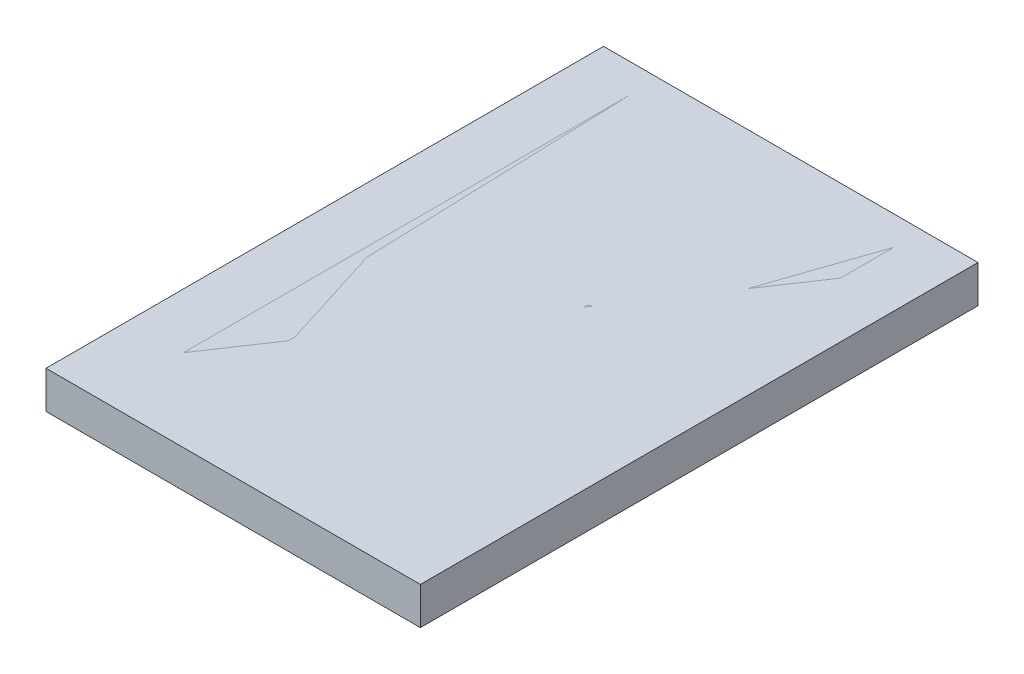
SolidWorks part; units mm, degrees
other "Part"
other "Stock"
ref_plane "Front Plane" through (0, 0, 0) normal (0, 0, 1) x (1, 0, 0)
ref_plane "Top Plane" through (0, 0, 0) normal (0, 1, 0) x (1, 0, 0)
ref_plane "Right Plane" through (0, 0, 0) normal (1, 0, 0) x (0, 0, -1)
sketch "Sketch1" plane through (0, 0, 0) normal (0, 1, 0) x (1, 0, 0)
  line L0 (28.2, 0) -> (28.2, -112.8) construction
  line L1 (0, 0) -> (56.4, 0)
  line L2 (0, 0) -> (0, -112.8)
  line L3 (0, -112.8) -> (56.4, -112.8)
  line L4 (56.4, 0) -> (56.4, -112.8)
  line L5 (0, -56.4) -> (56.4, -56.4) construction
  dimension "D1" = 56.4
  dimension "D2" = 112.8
extrude "Boss-Extrude1" add sketch "Sketch1" along normal blind 8
sketch "Sketch2" plane through (0, 8, 0) normal (0, 1, 0) x (1, 0, 0)
  line L0 (0, -56.4) -> (56.4, -56.4) construction
  line L1 (0, 0) -> (0, -112.8) construction
  line L2 (56.4, -112.8) -> (56.4, 0) construction
  line L3 (28.2, 0) -> (28.2, -112.8) construction
  line L4 (56.4, 0) -> (0, 0) construction
  line L5 (0, -112.8) -> (56.4, -112.8) construction
  line L6 (0, -28.2) -> (56.4, -28.2) construction
  circle A0 centre (28.2, -28.2) radius 19.25
  dimension "D2" = 38.5
  dimension "D1" = 28.2
extrude "Cut-Extrude1" cut sketch "Sketch2" against normal blind 2
sketch "Sketch3" plane through (0, 6, 0) normal (0, 1, 0) x (1, 0, 0)
  circle A0 centre (28.2, -28.2) radius 5
  dimension "D1" = 10
extrude "Cut-Extrude2" cut sketch "Sketch3" against normal through all
sketch "Sketch4" plane through (0, 8, 0) normal (0, 1, 0) x (1, 0, 0)
  line L0 (56.4, 0) -> (0, 0) construction
  line L1 (28.2, 0) -> (28.2, -86.1901) construction
  line L2 (0, -28.2) -> (56.4, -28.2) construction
  line L3 (0, 0) -> (0, -112.8) construction
  line L4 (56.4, -112.8) -> (56.4, 0) construction
  line L5 (0, -56.4) -> (56.4, -56.4) construction
  circle A0 centre (4.58, -4.58) radius 2.65
  circle A1 centre (51.82, -4.58) radius 2.65
  circle A2 centre (51.82, -51.82) radius 2.65
  circle A3 centre (4.58, -51.82) radius 2.65
  dimension "D4" = 5.3
  dimension "D1" = 23.62
  dimension "D2" = 28.2
  dimension "D3" = 23.62
extrude "Cut-Extrude3" cut sketch "Sketch4" against normal through all
sketch "Sketch5" plane through (0, 8, 0) normal (0, 1, 0) x (1, 0, 0)
  line L0 (0, -56.4) -> (56.4, -56.4) construction
  line L1 (0, 0) -> (0, -112.8) construction
  line L2 (56.4, -112.8) -> (56.4, 0) construction
  line L3 (0, -84.6) -> (56.4, -84.6) construction
  line L4 (28.2, 0) -> (28.2, -112.8) construction
  line L5 (56.4, 0) -> (0, 0) construction
  line L6 (0, -112.8) -> (56.4, -112.8) construction
  circle A0 centre (28.2, -84.6) radius 14
  point P14 (28.2, -84.6)
  dimension "D2" = 28
  dimension "D1" = 28.2
extrude "Cut-Extrude4" cut sketch "Sketch5" against normal through all
ref_plane "Plane1" through (0, 0, 56.4) normal (0, 0, 1) x (1, 0, 0)
mirror "Mirror1" about plane through (0, 0, 56.4) normal (0, 0, 1) of "Cut-Extrude3"
mirror "Mirror2" about plane through (0, 0, 56.4) normal (0, 0, 1) of "Cut-Extrude1"
fillet "Fillet2" radius 3 4 edges at (0, 4, 0) (56.4, 4, 0) (56.4, 4, 112.8) (0, 4, 112.8)
sketch "Sketch6" plane through (0, 8, 0) normal (0, 1, 0) x (1, 0, 0)
  line L0 (56.4, -109.8) -> (56.4, -3) construction
  line L1 (0, 0) -> (56.4, 0) construction
  line L2 (0, 0) -> (0, -112.8) construction
  line L3 (0, -112.8) -> (56.4, -112.8) construction
  line L4 (56.4, 0) -> (56.4, -112.8) construction
  line L5 (53.4, 0) -> (3, 0) construction
  line L6 (0, -3) -> (0, -109.8) construction
  line L7 (3, -112.8) -> (53.4, -112.8) construction
  line L8 (0, -56.4) -> (56.4, -56.4) construction
  line L9 (28.2, 0) -> (28.2, -112.8) construction
  line L10 (0, 0) -> (56.4, -112.8) construction
  line L11 (0, -112.8) -> (56.4, 0) construction
  line L13 (-11.8, 3.175) -> (68.2, 3.175)
  line L14 (-11.8, 3.175) -> (-11.8, -115.975)
  line L15 (-11.8, -115.975) -> (68.2, -115.975)
  line L16 (68.2, 3.175) -> (68.2, -115.975)
  line L17 (-11.8, 3.175) -> (68.2, -115.975) construction
  line L18 (-11.8, -115.975) -> (68.2, 3.175) construction
  point P16 (28.2, -56.4)
  dimension "D1" = 80
  dimension "D2" = 119.15
extrude "Boss-Extrude2" add sketch "Sketch6" against normal blind 8 separate body
sketch "Sketch8" plane through (0, 8, 0) normal (0, 1, 0) x (1, 0, 0)
  line L0 (-11.8, 3.175) -> (-11.8, -115.975) construction
  line L1 (-11.8, -115.975) -> (68.2, -115.975) construction
  line L2 (-11.8, 3.175) -> (-11.8, -115.975)
  line L3 (-11.8, -115.975) -> (68.2, -115.975)
